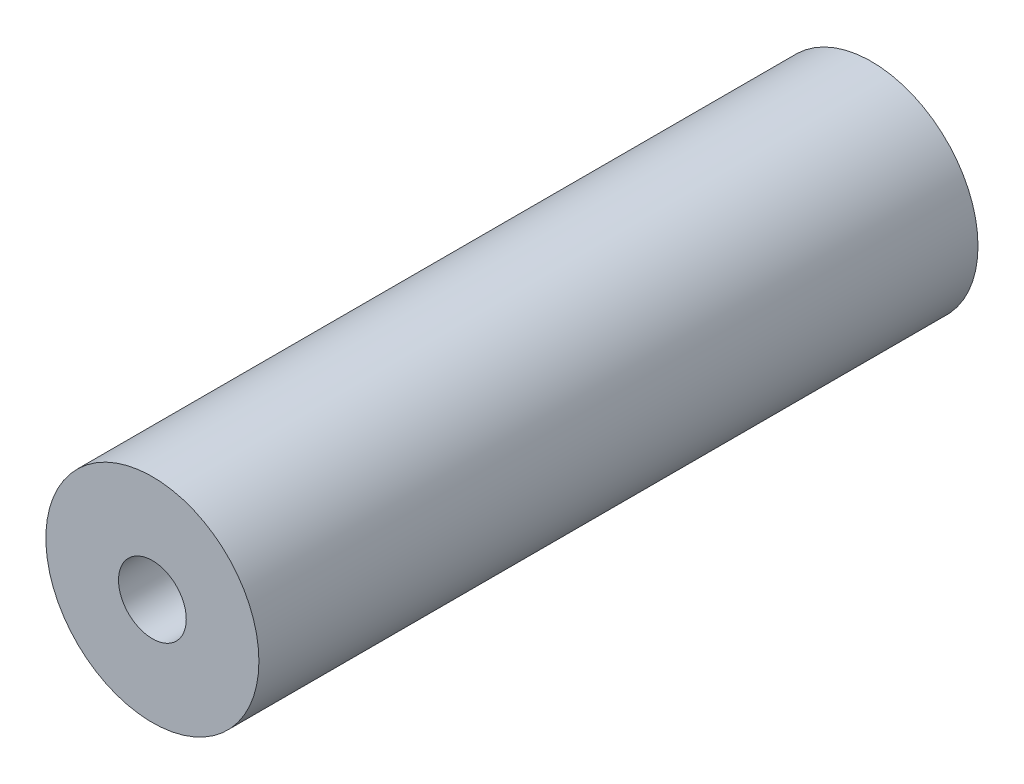
SolidWorks part; units mm, degrees
material "6061-T6 (SS)"
ref_plane "Front Plane" through (0, 0, 0) normal (0, 0, 1) x (1, 0, 0)
ref_plane "Top Plane" through (0, 0, 0) normal (0, 1, 0) x (1, 0, 0)
ref_plane "Right Plane" through (0, 0, 0) normal (1, 0, 0) x (0, 0, -1)
sketch "Sketch1" plane through (0, 0, 0) normal (0, 0, 1) x (1, 0, 0)
  circle A1 centre (0, 0) radius 6.35
  dimension "D2" = 12.7
extrude "Boss-Extrude1" add sketch "Sketch1" along normal mid plane 42.8625 contours A1 region at (0, 0, 0)
hole_wizard "#10-32 Tapped Hole1" positions "3DSketch1" profile "Sketch2" tap size "#10-32" standard "ANSI Inch"
sketch3d "3DSketch1"
  line L0 (0, 0, 21.4312) -> (0, 0, -21.4312) construction
  point P0 (0, 0, 21.4312)
  point P4 (0, 0, -21.4312)
sketch "Sketch2" plane through (0, 0, 21.4312) normal (1, 0, 0) x (0, -1, 0)
  line L0 (0, 0) -> (0, 13.2428)
  line L1 (0, 13.2428) -> (2.0193, 12.0294)
  line L2 (2.0193, 12.0294) -> (2.0193, 0)
  line L5 (2.0193, 0) -> (0, 0)
  line L10 (0, 13.2428) -> (-2.0193, 12.0294) construction
  line L11 (0, -6.35) -> (0, 107.95) construction
  dimension "Tap Drill Dia." = 4.0386
  dimension "Tap Drill Depth" = 12.0294
  dimension "Drill Angle" = 118
cosmetic thread "Hole Thread1"
cosmetic thread "Hole Thread2"
